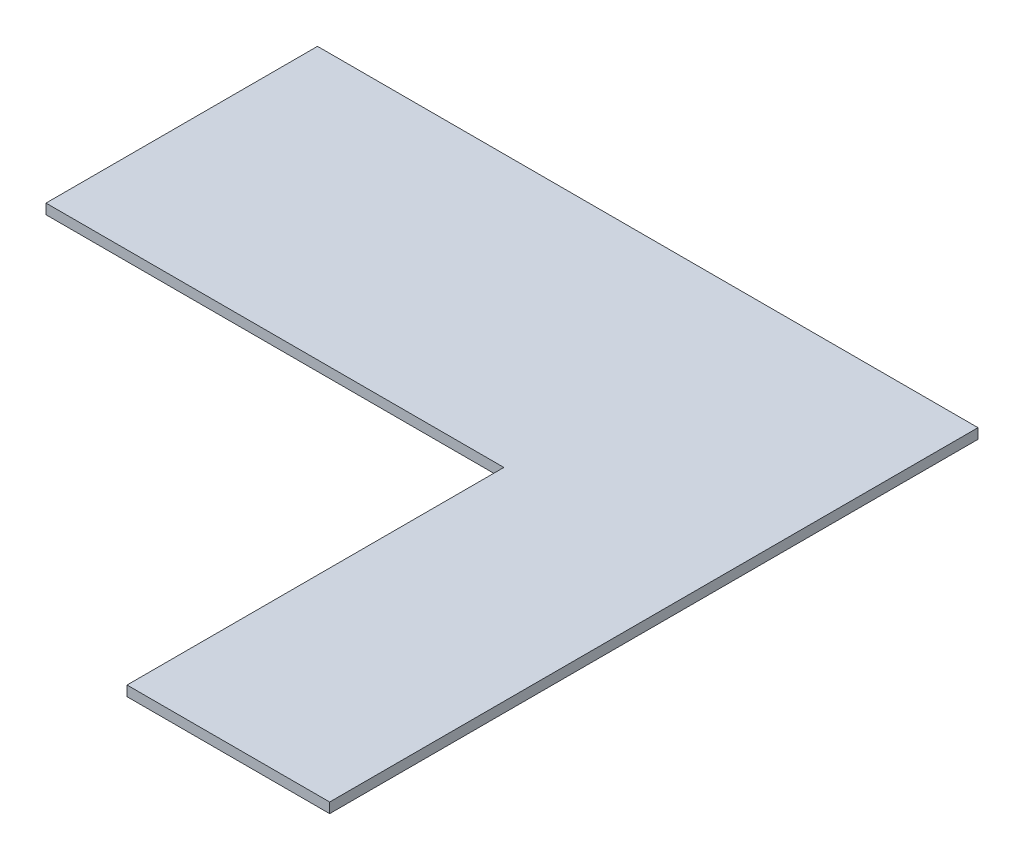
SolidWorks part; units mm, degrees
ref_plane "Спереди" through (0, 0, 0) normal (0, 0, 1) x (1, 0, 0)
ref_plane "Сверху" through (0, 0, 0) normal (0, 1, 0) x (1, 0, 0)
ref_plane "Справа" through (0, 0, 0) normal (1, 0, 0) x (0, 0, -1)
sketch "Эскиз1" plane through (0, 0, 0) normal (0, 1, 0) x (1, 0, 0)
  line L0 (0, 0) -> (0, 670)
  line L1 (0, 670) -> (1630, 670)
  line L2 (1630, 670) -> (1630, -930)
  line L3 (1630, -930) -> (1130, -930)
  line L4 (1130, -930) -> (1130, 0)
  line L5 (1130, 0) -> (0, 0)
  point P3 (0, 0)
extrude "Бобышка-Вытянуть1" add sketch "Эскиз1" along normal blind 25
